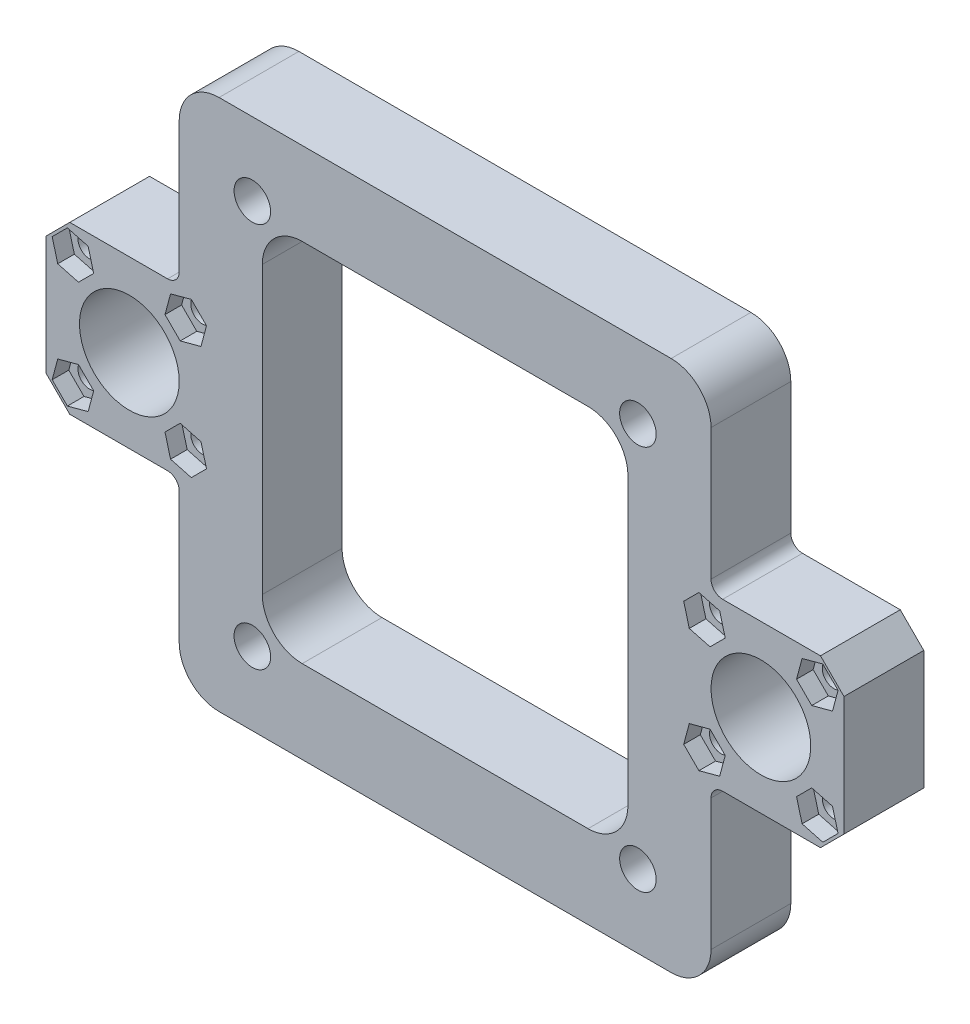
SolidWorks part; units mm, degrees
ref_plane "Front Plane" through (0, 0, 0) normal (0, 0, 1) x (1, 0, 0)
ref_plane "Top Plane" through (0, 0, 0) normal (0, 1, 0) x (1, 0, 0)
ref_plane "Right Plane" through (0, 0, 0) normal (1, 0, 0) x (0, 0, -1)
sketch "Sketch1" plane through (0, 0, 0) normal (0, 0, 1) x (1, 0, 0)
  line L0 (-47.5, 0) -> (47.5, 0) construction
  line L1 (0, 0) -> (0, 17.3262) construction
  line L2 (-56.4645, 12.5) -> (-41.75, 12.5)
  line L3 (-40, 14.25) -> (-40, 34)
  line L12 (-56.4645, 12.5) -> (-60, 8.9645)
  line L13 (-60, 8.9645) -> (-60, -8.9645)
  line L14 (34, 40) -> (-34, 40)
  line L15 (60, 8.9645) -> (60, -8.9645)
  line L16 (56.4645, 12.5) -> (60, 8.9645)
  line L17 (56.4645, 12.5) -> (41.75, 12.5)
  line L18 (40, 14.25) -> (40, 34)
  line L19 (-56.4645, -12.5) -> (-60, -8.9645)
  line L20 (-56.4645, -12.5) -> (-41.75, -12.5)
  line L21 (-40, -14.25) -> (-40, -34)
  line L22 (34, -40) -> (-34, -40)
  line L23 (40, -14.25) -> (40, -34)
  line L24 (56.4645, -12.5) -> (41.75, -12.5)
  line L25 (56.4645, -12.5) -> (60, -8.9645)
  line L26 (-55.9853, 8.4853) -> (-39.0147, -8.4853) construction
  line L27 (-55.9853, -8.4853) -> (-39.0147, 8.4853) construction
  circle A0 centre (-47.5, 0) radius 7.5
  arc A12 (-41.75, 12.5) -> (-40, 14.25) centre (-41.75, 14.25) ccw
  arc A13 (-40, 34) -> (-34, 40) centre (-34, 34) cw
  arc A14 (41.75, 12.5) -> (40, 14.25) centre (41.75, 14.25) cw
  arc A15 (40, 34) -> (34, 40) centre (34, 34) ccw
  arc A16 (-41.75, -12.5) -> (-40, -14.25) centre (-41.75, -14.25) cw
  arc A17 (-40, -34) -> (-34, -40) centre (-34, -34) ccw
  arc A18 (40, -34) -> (34, -40) centre (34, -34) cw
  arc A19 (41.75, -12.5) -> (40, -14.25) centre (41.75, -14.25) ccw
  circle A20 centre (47.5, 0) radius 7.5
  circle A21 centre (-55.9853, 8.4853) radius 1.75
  circle A22 centre (-39.0147, -8.4853) radius 1.75
  circle A23 centre (-39.0147, 8.4853) radius 1.75
  circle A24 centre (-55.9853, -8.4853) radius 1.75
  circle A25 centre (39.0147, -8.4853) radius 1.75
  circle A26 centre (55.9853, -8.4853) radius 1.75
  circle A27 centre (55.9853, 8.4853) radius 1.75
  circle A28 centre (39.0147, 8.4853) radius 1.75
  circle A29 centre (-29, 29) radius 2.75
  circle A33 centre (29, 29) radius 2.75
  circle A34 centre (29, -29) radius 2.75
  circle A35 centre (-29, -29) radius 2.75
  point P28 (0, 40)
  point P29 (-60, 0)
  point P44 (60, 0)
  dimension "D2" = 15
  dimension "D3" = 25
  dimension "D6" = 1.75
  dimension "D11" = 3.5
  dimension "D13" = 6
  dimension "D15" = 5.5
  dimension "D1" = 95
  dimension "D4" = 120
  dimension "D5" = 40
  dimension "D7" = 135
  dimension "D8" = 80
  dimension "D9" = 5
  dimension "D10" = 24
  dimension "D12" = 135
  dimension "D14" = 58
  dimension "D16" = 58
extrude "Boss-Extrude1" add sketch "Sketch1" along normal blind 12
sketch "Sketch2" plane through (0, 0, 12) normal (0, 0, 1) x (1, 0, 0)
  line L0 (-21.5, 21.5) -> (21.5, -21.5) construction
  line L1 (-21.5, 27.5) -> (21.5, 27.5)
  line L2 (-27.5, 21.5) -> (-27.5, -21.5)
  line L3 (-21.5, -27.5) -> (21.5, -27.5)
  line L4 (27.5, 21.5) -> (27.5, -21.5)
  arc A0 (-27.5, -21.5) -> (-21.5, -27.5) centre (-21.5, -21.5) ccw
  arc A1 (21.5, -27.5) -> (27.5, -21.5) centre (21.5, -21.5) ccw
  arc A2 (27.5, 21.5) -> (21.5, 27.5) centre (21.5, 21.5) ccw
  arc A3 (-21.5, 27.5) -> (-27.5, 21.5) centre (-21.5, 21.5) ccw
  dimension "D1" = 6
  dimension "D2" = 55
extrude "Cut-Extrude1" cut sketch "Sketch2" against normal through all both and the other way through all
sketch "Sketch3" plane through (0, 0, 12) normal (0, 0, 1) x (1, 0, 0)
  line L0 (-56.4645, 12.5) -> (-60, 8.9645) construction
  line L1 (-55.1485, 5.3623) -> (-52.8623, 7.6485)
  line L2 (-52.8623, 7.6485) -> (-53.6991, 10.7715)
  line L3 (-53.6991, 10.7715) -> (-56.8221, 11.6083)
  line L4 (-56.8221, 11.6083) -> (-59.1083, 9.3221)
  line L5 (-59.1083, 9.3221) -> (-58.2715, 6.1991)
  line L6 (-58.2715, 6.1991) -> (-55.1485, 5.3623)
  line L7 (-42.1377, 7.6485) -> (-39.8515, 5.3623)
  line L8 (-39.8515, 5.3623) -> (-36.7285, 6.1991)
  line L9 (-36.7285, 6.1991) -> (-35.8917, 9.3221)
  line L10 (-35.8917, 9.3221) -> (-38.1779, 11.6083)
  line L11 (-38.1779, 11.6083) -> (-41.3009, 10.7715)
  line L12 (-41.3009, 10.7715) -> (-42.1377, 7.6485)
  line L13 (-39.8515, -5.3623) -> (-42.1377, -7.6485)
  line L14 (-42.1377, -7.6485) -> (-41.3009, -10.7715)
  line L15 (-41.3009, -10.7715) -> (-38.1779, -11.6083)
  line L16 (-38.1779, -11.6083) -> (-35.8917, -9.3221)
  line L17 (-35.8917, -9.3221) -> (-36.7285, -6.1991)
  line L18 (-36.7285, -6.1991) -> (-39.8515, -5.3623)
  line L19 (-52.8623, -7.6485) -> (-55.1485, -5.3623)
  line L20 (-55.1485, -5.3623) -> (-58.2715, -6.1991)
  line L21 (-58.2715, -6.1991) -> (-59.1083, -9.3221)
  line L22 (-59.1083, -9.3221) -> (-56.8221, -11.6083)
  line L23 (-56.8221, -11.6083) -> (-53.6991, -10.7715)
  line L24 (-53.6991, -10.7715) -> (-52.8623, -7.6485)
  circle A0 centre (-55.9853, 8.4853) radius 2.8 construction
  circle A1 centre (-55.9853, 8.4853) radius 1.75 construction
  circle A2 centre (-47.5, 0) radius 7.5 construction
  circle A3 centre (-47.5, 0) radius 7.5 construction
  circle A4 centre (-39.0147, 8.4853) radius 2.8 construction
  circle A5 centre (-39.0147, -8.4853) radius 2.8 construction
  circle A6 centre (-55.9853, -8.4853) radius 2.8 construction
  point P42 (-47.5, 0)
  dimension "D1" = 5.6
  dimension "D2" = 4
extrude "Cut-Extrude2" cut sketch "Sketch3" against normal blind 2.5
mirror "Mirror1" about plane through (0, 0, 0) normal (1, 0, 0) of "Cut-Extrude2"
